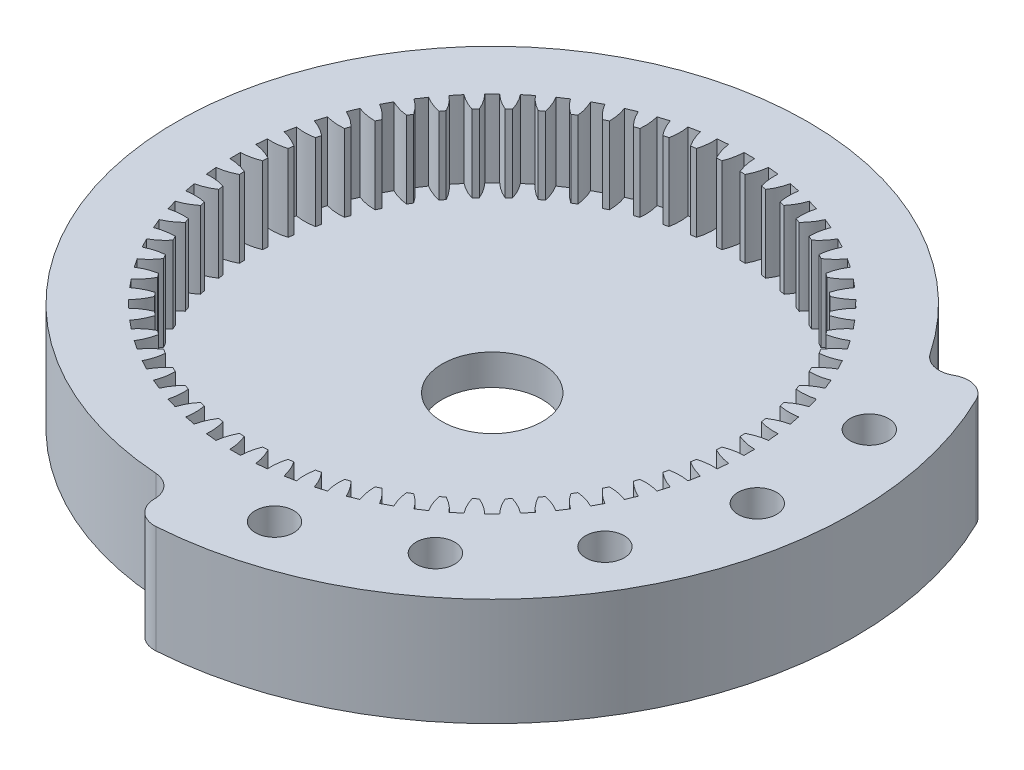
SolidWorks part; units mm, degrees
ref_plane "Front Plane" through (0, 0, 0) normal (0, 0, 1) x (1, 0, 0)
ref_plane "Top Plane" through (0, 0, 0) normal (0, 1, 0) x (1, 0, 0)
ref_plane "Right Plane" through (0, 0, 0) normal (1, 0, 0) x (0, 0, -1)
sketch "Sketch1" plane through (0, 0, 0) normal (0, 1, 0) x (1, 0, 0)
  circle A0 centre (0, 0) radius 16
  circle A1 centre (0, 0) radius 16.7
  circle A2 centre (0, 0) radius 15.5
  dimension "D1" = 32
  dimension "D2" = 33.4
  dimension "D3" = 1.2
extrude "Boss-Extrude1" add sketch "Sketch1" along normal mid plane 5 contours A1 A0 | A0 A2 | A2 region at (-15.5475, 0, 0) region at (-16.2277, 0, 0) region at (0, 0, 0)
sketch "Sketch7" plane through (0, 0, 0) normal (0, 1, 0) x (1, 0, 0)
  line L0 (16.7, 0) -> (-16.7, 0) construction
  line L1 (0, 16.7) -> (0, -16.7) construction
  circle A0 centre (0, 0) radius 16.7 construction
  point P7 (0, 0)
sketch "Sketch4" plane through (0, 0, 0) normal (0, 1, 0) x (1, 0, 0)
  line L0 (0, 0) -> (0, -23.5) construction
  line L10 (0, 0) -> (20.3516, 11.75) construction
  line L11 (20.3516, 11.75) -> (17.7535, 10.25)
  line L12 (0, -23.5) -> (0, -20.5)
  circle A2 centre (0, 0) radius 15.5 construction
  circle A3 centre (0, 0) radius 15.5
  arc A4 (17.7535, 10.25) -> (0, -20.5) centre (0, 0) ccw
  circle A9 centre (0, 0) radius 23.5 construction
  arc A10 (20.3516, 11.75) -> (0, -23.5) centre (0, 0) cw
  dimension "D1" = 5
  dimension "D3" = 120
  dimension "D2" = 3
extrude "Boss-Extrude2" add sketch "Sketch4" along normal mid plane 5
sketch "Sketch3" plane through (0, 0, 0) normal (0, 1, 0) x (1, 0, 0)
  line L0 (0, 0) -> (0, 16.7) construction
  line L1 (-0.3927, 15.9952) -> (0.3927, 15.9952) construction
  line L2 (-0.3434, 15.4962) -> (0, 0) construction
  line L3 (0, 13.7683) -> (-0.5155, 16.692) construction
  line L4 (0, 0) -> (0.8194, 16.6799) construction
  line L5 (0.3927, 15.9952) -> (1.177, 15.9566) construction
  line L6 (0, 15.5) -> (0, 16.7) construction
  line L7 (0.3434, 15.4962) -> (0.3434, 16.7) construction
  line L8 (0.3434, 16.0981) -> (-0.3121, 16.0981) construction
  arc A1 (-0.5957, 16.6894) -> (-0.3434, 15.4962) centre (-3.6364, 15.4232) cw construction
  arc A2 (0.5957, 16.6894) -> (0.3434, 15.4962) centre (3.6364, 15.4232) ccw construction
  circle A3 centre (0, 0) radius 15.5 construction
  arc A4 (0.3434, 15.4962) -> (-0.3434, 15.4962) centre (0, 0) ccw construction
  circle A5 centre (0, 0) radius 16 construction
  circle A6 centre (0, 0) radius 16.7 construction
  arc A7 (0.5957, 15.5068) -> (-0.5957, 15.5068) centre (0, 32.1962) cw
  arc A8 (0.5957, 16.6894) -> (-0.5957, 16.6894) centre (0, 0) ccw construction
  arc A9 (-0.5957, 15.5068) -> (-0.3434, 16.7) centre (-3.6364, 16.773) ccw
  arc A10 (0.5957, 15.5068) -> (0.3434, 16.7) centre (3.6364, 16.773) cw
  arc A11 (0.3434, 16.7) -> (-0.3434, 16.7) centre (0, 32.1962) cw
  dimension "D3" = 2.813
  dimension "D2" = 10
extrude "Cut-Extrude1" cut sketch "Sketch3" against normal through all both and the other way through all
pattern_circular "CirPattern1" count 64 over 360 about axis through (0, 2.5, 0) along (0, 1, 0) of "Cut-Extrude1"
sketch "Sketch5" plane through (0, 0, 0) normal (0, 1, 0) x (1, 0, 0)
  circle A0 centre (0, 0) radius 15.5183
extrude "Cut-Extrude2" cut sketch "Sketch5" against normal through all both and the other way through all
sketch "Sketch8" plane through (0, -2.5, 0) normal (0, -1, 0) x (1, 0, 0)
  line L2 (0, 23.5) -> (0, 20.5)
  line L6 (0, 23.5) -> (0, 20.5)
  line L8 (17.7535, -10.25) -> (20.3516, -11.75)
  line L9 (17.7535, -10.25) -> (20.3516, -11.75)
  circle A0 centre (0, 0) radius 3.25
  arc A3 (20.3516, -11.75) -> (0, 23.5) centre (0, 0) ccw
  arc A4 (20.3516, -11.75) -> (0, 23.5) centre (0, 0) ccw
  arc A5 (0, 20.5) -> (17.7535, -10.25) centre (0, 0) ccw
  arc A7 (0, 20.5) -> (17.7535, -10.25) centre (0, 0) ccw
  point P1 (0, 0)
  dimension "D2" = 6.5
  dimension "D1" = 0
extrude "Boss-Extrude3" add sketch "Sketch8" along normal blind 2
sketch "Sketch6" plane through (0, 2.5, 0) normal (0, 1, 0) x (1, 0, 0)
  line L0 (0, 0) -> (5.1764, -19.3185) construction
  line L2 (0, -16.7) -> (0, 16.7) construction
  circle A3 centre (5.1764, -19.3185) radius 1.25
  point P11 (0, 0)
  dimension "D2" = 15
  dimension "D1" = 2.5
  dimension "D3" = 20
extrude "Cut-Extrude3" cut sketch "Sketch6" against normal through all
pattern_circular "CirPattern2" count 5 over 90 about axis through (0, -2.5, 0) along (0, -1, 0) of "Cut-Extrude3" reverse direction yes
fillet "Fillet1" radius 1.5 4 edges at (17.7535, -1, -10.25) (20.3516, -1, -11.75) (0, -1, 23.5) (0, -1, 20.5)
equation "\"Module\"= .5"
equation "\"Number of Teeth\"=64"
equation "\"D1@Sketch1\"=\"Module\"* \"Number of Teeth\""
equation "\"D2@Sketch1\"=(\"Number of Teeth\" + 2) * \"Module\" + .4"
equation "\"D3@Sketch1\"=\"Module\" * if( \"Module\" => 1.25, 2.25, 2.4)"
equation "\"D3@Sketch3\"=180 / \"Number of Teeth\""
equation "\"D1@CirPattern1\"=\"Number of Teeth\""
